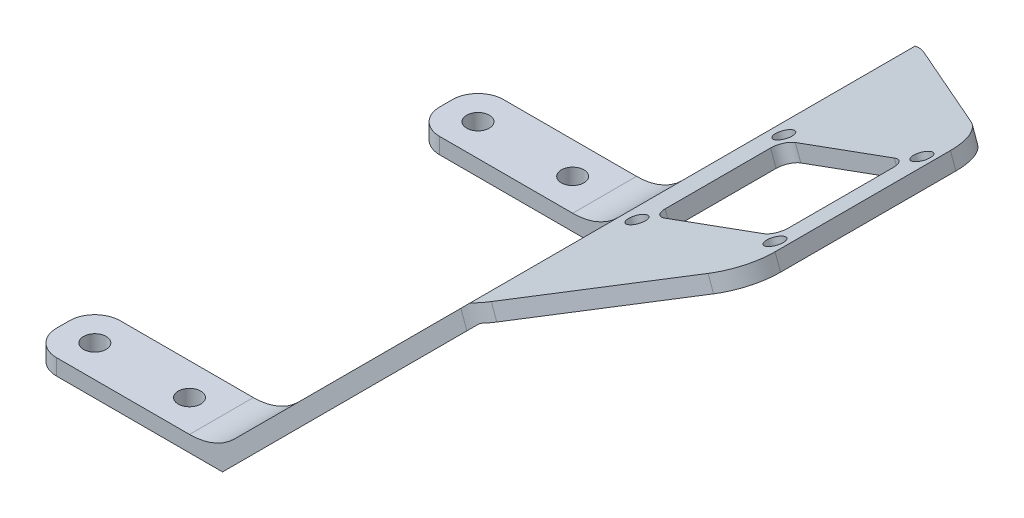
SolidWorks part; units mm, degrees
ref_plane "Front Plane" through (0, 0, 0) normal (0, 0, 1) x (1, 0, 0)
ref_plane "Top Plane" through (0, 0, 0) normal (0, 1, 0) x (1, 0, 0)
ref_plane "Right Plane" through (0, 0, 0) normal (1, 0, 0) x (0, 0, -1)
sketch "Sketch1" plane through (0, 0, 0) normal (0, 0, 1) x (1, 0, 0)
  line L0 (0, 0) -> (38.1, 0)
  line L1 (38.1, 0) -> (88.9, 50.8)
  line L2 (88.9, 50.8) -> (122.0529, 62.8667)
  line L3 (0, 0) -> (0, 3.175)
  line L4 (0, 3.175) -> (36.7849, 3.175)
  line L5 (36.7849, 3.175) -> (87.1527, 53.5428)
  line L6 (87.1527, 53.5428) -> (120.967, 65.8502)
  line L7 (120.967, 65.8502) -> (122.0529, 62.8667)
  point P9 (0, 0)
  point P10 (102.3926, 45.8379)
  point P11 (71.7627, 37.5919)
  point P12 (102.0896, 44.8708)
  dimension "D1" = 3.175
  dimension "D2" = 3.175
  dimension "D3" = 3.175
  dimension "D4" = 50.8
  dimension "D5" = 50.8
  dimension "D6" = 155
  dimension "D7" = 38.1
  dimension "D8" = 35.2806
extrude "Boss-Extrude1" add sketch "Sketch1" against normal blind 88.9
sketch "Sketch2" plane through (0, 0, 0) normal (-1, 0, 0) x (0, 0, 1)
  line L0 (-88.9, 0) -> (0, 0) construction
  line L1 (-76.2, 0) -> (-12.7, 0)
  line L2 (-76.2, 0) -> (-76.2, 76.5777)
  line L3 (-76.2, 76.5777) -> (-12.7, 76.5777)
  line L4 (-12.7, 0) -> (-12.7, 76.5777)
  point P6 (0, 0)
  point P9 (-44.45, 0)
  dimension "D1" = 63.5
sketch "Sketch3" plane through (-5.9275, 16.2856, 0) normal (0.342, -0.9397, 0) x (0.9397, 0.342, 0)
  line L0 (136.1939, -88.9) -> (136.1939, 0) construction
  line L1 (103.9486, -29.845) -> (133.1586, -29.845)
  line L2 (103.9486, -29.845) -> (103.9486, -59.055)
  line L3 (103.9486, -59.055) -> (133.1586, -59.055)
  line L4 (133.1586, -29.845) -> (133.1586, -59.055)
  line L5 (100.9133, 0) -> (136.1939, 0) construction
  line L6 (131.5711, -31.4325) -> (131.5711, -57.4675)
  line L7 (105.5361, -57.4675) -> (131.5711, -57.4675)
  line L8 (105.5361, -31.4325) -> (105.5361, -57.4675)
  line L9 (105.5361, -31.4325) -> (131.5711, -31.4325)
  circle A0 centre (133.1586, -29.845) radius 1.7463
  circle A1 centre (103.9486, -29.845) radius 1.7462
  circle A2 centre (103.9486, -59.055) radius 1.7463
  circle A3 centre (133.1586, -59.055) radius 1.7462
  point P4 (136.1939, -44.45)
  point P5 (133.1586, -44.45)
  point P12 (118.5536, 0)
  point P13 (118.5536, -29.845)
  point P16 (0, 0)
  dimension "D2" = 3.4925
  dimension "D3" = 3.4925
  dimension "D4" = 3.4925
  dimension "D5" = 3.4925
  dimension "D1" = 29.21
  dimension "D6" = 1.5875
extrude "Cut-Extrude2" cut sketch "Sketch3" against normal blind 74.93 contours L1 A1 L2 | L2 A1 L1 | L9 L8 L7 L6 | L4 A0 L1 | L1 A0 L4 | L3 A3 L4 | L4 A3 L3 | L2 A2 L3 | L3 A2 L2
fillet "Fillet1" radius 2.54 4 edges at (92.7011, 53.8729, -31.4325) (117.166, 62.7773, -31.4325) (92.7011, 53.8729, -57.4675) (117.166, 62.7773, -57.4675)
sketch "Sketch4" plane through (-5.9275, 16.2856, 0) normal (0.342, -0.9397, 0) x (0.9397, 0.342, 0)
  line L0 (136.1939, -21.2725) -> (100.9133, 0)
  line L1 (136.1939, -88.9) -> (136.1939, 0) construction
  line L2 (35.8023, 0) -> (100.9133, 0) construction
  line L3 (129.0311, -31.4325) -> (108.0761, -31.4325) construction
  line L4 (48.2557, -12.7) -> (35.6524, -12.7)
  line L5 (136.1939, -88.9) -> (136.1939, 0) construction
  line L6 (100.9133, -44.45) -> (48.2557, -12.7)
  line L7 (100.9133, -88.9) -> (100.9133, 0) construction
  line L8 (35.6524, -88.9) -> (35.6524, 0) construction
  line L9 (35.6524, -88.9) -> (35.6524, 0)
  line L10 (100.9133, -12.7) -> (136.1939, -12.7)
  line L11 (100.9133, -12.7) -> (136.1939, -12.7) construction
  line L12 (100.9133, 0) -> (136.1939, 0)
  line L13 (136.1939, 0) -> (136.1939, -21.2725)
  line L14 (100.9133, -44.45) -> (136.1939, -44.45) construction
  line L15 (48.2557, -76.2) -> (35.6524, -76.2)
  line L16 (100.9133, -44.45) -> (48.2557, -76.2)
  line L17 (136.1939, -88.9) -> (136.1939, -67.6275)
  line L18 (100.9133, -88.9) -> (136.1939, -88.9)
  line L19 (136.1939, -67.6275) -> (100.9133, -88.9)
  line L20 (100.9133, -88.9) -> (35.6524, -88.9)
  line L21 (100.9133, 0) -> (35.6524, 0)
  point P27 (0, 0)
  line M13 (136.1939, 0) -> (100.9133, 0)
  line M14 (100.9133, 0) -> (100.9133, -88.9)
  line M15 (100.9133, -88.9) -> (136.1939, -88.9)
  line M16 (136.1939, -88.9) -> (136.1939, 0)
  dimension "D1" = 10.16
  dimension "D2" = 12.7
extrude "Cut-Extrude3" cut sketch "Sketch4" against normal through all both and the other way through all contours L0 M16 M13 M14 | L19 M16 M14 M15 | L16 L6 L4 L9 L15
fillet "Fillet2" radius 12.7 1 edges at (88.357, 52.2918, -44.45)
fillet "Fillet3" radius 12.7 2 edges at (36.7849, 3.175, -6.35) (36.7849, 3.175, -82.55)
fillet "Fillet4" radius 10.16 4 edges at (88.357, 52.2918, -88.9) (121.51, 64.3584, -67.6275) (121.51, 64.3584, -21.2725) (88.357, 52.2918, 0)
sketch "Sketch5" plane through (0, 3.175, 0) normal (0, 1, 0) x (1, 0, 0)
  line L0 (38.1, 76.2) -> (0, 76.2)
  line L1 (0, 76.2) -> (0, 12.7) construction
  line L2 (0, 76.2) -> (0, 12.7) construction
  line L3 (38.1, 12.7) -> (0, 12.7)
  line L4 (36.7849, 12.7) -> (37.9405, 12.7) construction
  line L5 (37.9405, 12.7) -> (37.9405, 76.2) construction
  line L6 (37.9405, 76.2) -> (36.7849, 76.2) construction
  line L7 (0, 0) -> (31.5244, 0) construction
  line L8 (31.5244, 0) -> (31.5244, 12.7) construction
  line L9 (31.5244, 12.7) -> (36.7849, 12.7) construction
  line L10 (36.7849, 76.2) -> (31.5244, 76.2) construction
  line L11 (31.5244, 76.2) -> (31.5244, 88.9) construction
  line L12 (31.5244, 88.9) -> (0, 88.9) construction
  line L13 (0, 88.9) -> (0, 0) construction
  line L14 (36.7849, 12.7) -> (37.9405, 12.7)
  line L15 (37.9405, 12.7) -> (37.9405, 76.2)
  line L16 (37.9405, 76.2) -> (36.7849, 76.2)
  line L17 (0, 0) -> (31.5244, 0)
  line L18 (31.5244, 0) -> (31.5244, 12.7)
  line L19 (31.5244, 12.7) -> (36.7849, 12.7)
  line L20 (36.7849, 76.2) -> (31.5244, 76.2)
  line L21 (31.5244, 76.2) -> (31.5244, 88.9)
  line L22 (31.5244, 88.9) -> (0, 88.9)
  line L23 (0, 88.9) -> (0, 0)
  line M13 (31.5244, 12.7) -> (36.7849, 12.7)
  line M14 (36.7849, 12.7) -> (36.7849, 76.2)
  line M15 (36.7849, 76.2) -> (31.5244, 76.2)
  line M18 (0, 88.9) -> (0, 0)
extrude "Cut-Extrude4" cut sketch "Sketch5" against normal through all both contours L3 L0 M13 M14 M15 M18 | L3 L15 L0 M14
fillet "Fillet5" radius 5.08 4 edges at (0, 1.5875, 0) (0, 1.5875, -12.7) (0, 1.5875, -76.2) (0, 1.5875, -88.9)
sketch "Sketch6" plane through (0, 3.175, 0) normal (0, 1, 0) x (1, 0, 0)
  line L0 (0, 83.82) -> (0, 81.28) construction
  line L1 (31.5244, 76.2) -> (31.5244, 88.9) construction
  line L2 (0, 7.62) -> (0, 5.08) construction
  circle A0 centre (6.35, 82.55) radius 2.2479
  circle A1 centre (25.1744, 82.55) radius 2.2479
  circle A2 centre (6.35, 6.35) radius 2.2479
  circle A3 centre (25.1744, 6.35) radius 2.2479
  point P12 (0, 6.35)
  point P13 (0, 0)
  point P14 (0, 82.55)
  point P17 (0, 0)
  point P18 (0, 0)
  point P19 (0, 0)
  point P20 (0, 0)
  point P21 (0, 0)
  point P22 (0, 0)
  dimension "D1" = 4.4958
  dimension "D2" = 4.4958
  dimension "D3" = 4.4958
  dimension "D4" = 4.4958
  dimension "D5" = 6.35
  dimension "D6" = 6.35
extrude "Cut-Extrude5" cut sketch "Sketch6" against normal through all both contours A0 | A1 | A2 | A3
